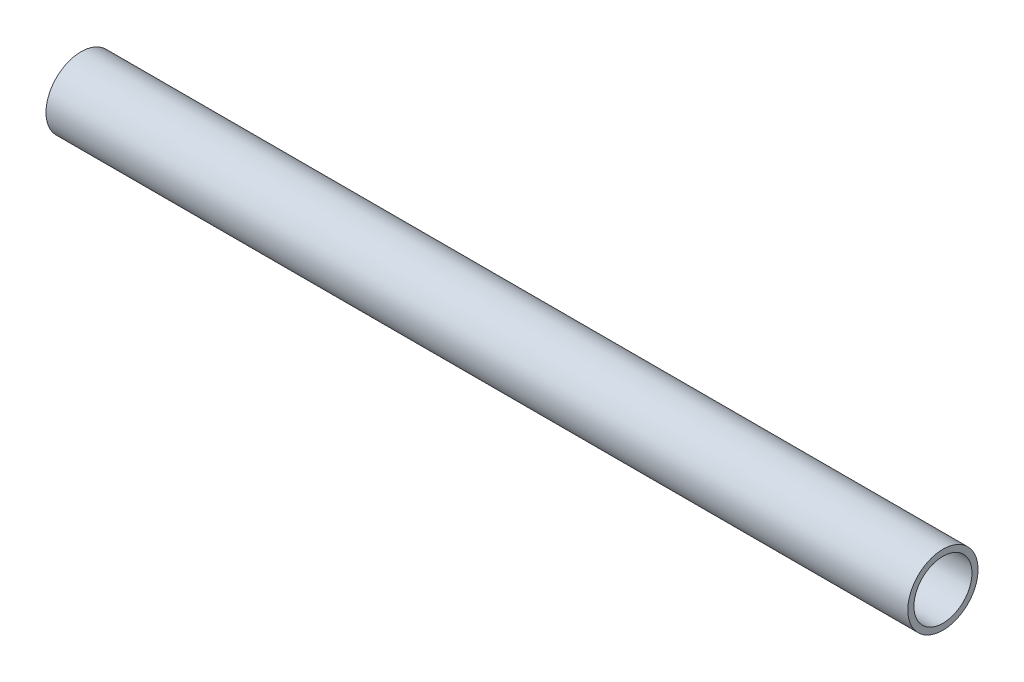
SolidWorks part; units mm, degrees
material "6061 Alloy"
ref_plane "Front Plane" through (0, 0, 0) normal (0, 0, 1) x (1, 0, 0)
ref_plane "Top Plane" through (0, 0, 0) normal (0, 1, 0) x (1, 0, 0)
ref_plane "Right Plane" through (0, 0, 0) normal (1, 0, 0) x (0, 0, -1)
sketch "Sketch1" plane through (0, 0, 0) normal (1, 0, 0) x (0, 0, -1)
  circle A0 centre (0, 0) radius 9.525
  circle A1 centre (0, 0) radius 7.874
  dimension "D1" = 19.05
  dimension "D2" = 15.748
extrude "Boss-Extrude1" add sketch "Sketch1" along normal mid plane 233.68
